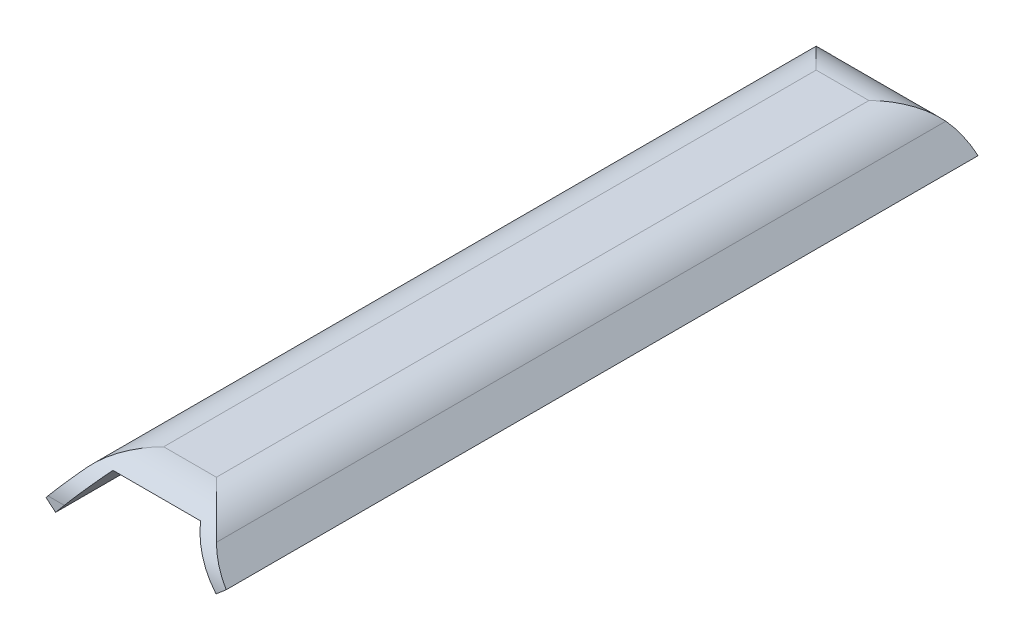
SolidWorks part; units mm, degrees
ref_plane "Front Plane" through (0, 0, 0) normal (0, 0, 1) x (1, 0, 0)
ref_plane "Top Plane" through (0, 0, 0) normal (0, 1, 0) x (1, 0, 0)
ref_plane "Right Plane" through (0, 0, 0) normal (1, 0, 0) x (0, 0, -1)
sketch "Sketch1" plane through (0, 0, 0) normal (0, 0, 1) x (1, 0, 0)
  line L0 (0, 0) -> (70, 0)
  line L1 (0, 0) -> (-32.1394, -38.3022)
  line L2 (70, 0) -> (95.7115, -30.6418)
  dimension "D1" = 50
  dimension "D2" = 40
  dimension "D3" = 130
  dimension "D4" = 130
extrude "Extrude-Thin1" add sketch "Sketch1" along normal blind 600 thin contours L2 L0 L1 thin type one direction wall 10
fillet "Fillet2" radius 40 4 edges at (74.6631, 10, 300) (35, 10, 600) (-4.6631, 10, 300) (35, 10, 0)
sketch "Sketch2" plane through (0, 10, 0) normal (0, 1, 0) x (1, 0, 0)
  line L0 (35, -40) -> (56.0108, -40) construction
  line L1 (56.0108, -40) -> (13.9892, -40) construction
  line L2 (86.6525, -9.3582) -> (56.0108, -40) construction
  line L3 (45.5054, -40) -> (45.5054, -560) construction
  line L4 (13.9892, -560) -> (56.0108, -560) construction
  point P10 (45.5054, -100)
  point P11 (45.5054, -200)
  point P12 (45.5054, -400)
  point P13 (45.5054, -500)
  point P14 (45.5054, -300)
  dimension "D1" = 100
  dimension "D2" = 100
  dimension "D3" = 200
  dimension "D4" = 200
